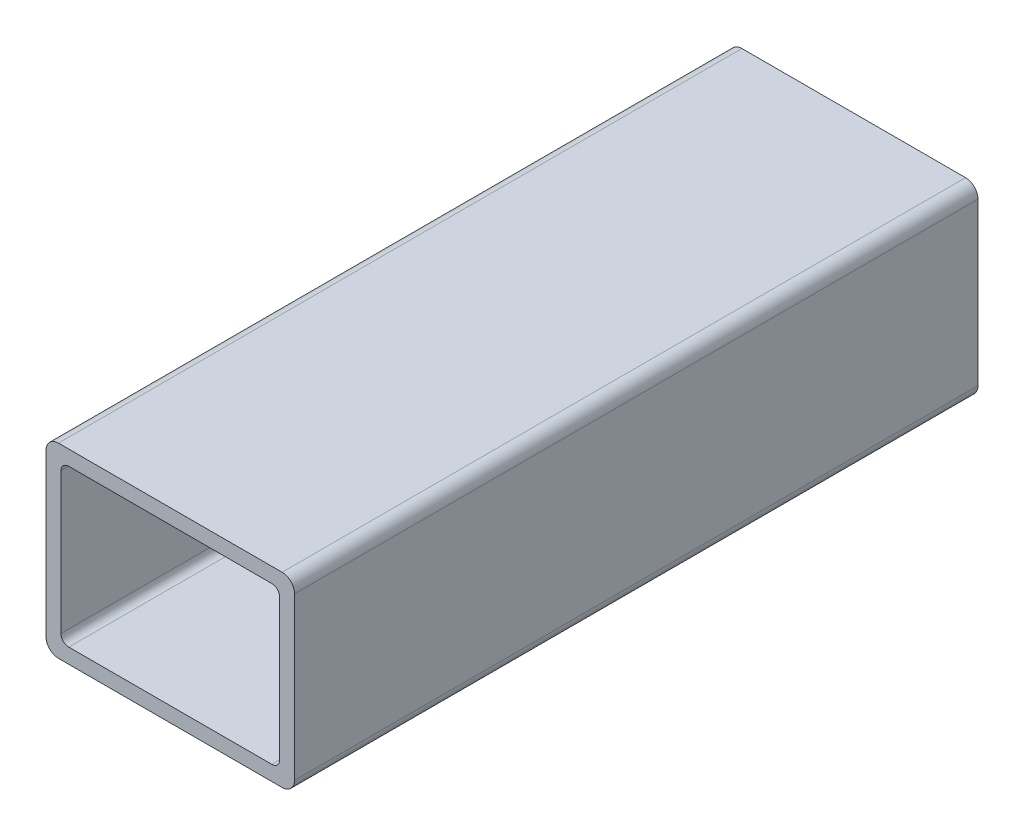
SolidWorks part; units mm, degrees
ref_plane "Front" through (0, 0, 0) normal (0, 0, 1) x (1, 0, 0)
ref_plane "Top" through (0, 0, 0) normal (0, 1, 0) x (1, 0, 0)
ref_plane "Right" through (0, 0, 0) normal (1, 0, 0) x (0, 0, -1)
sketch "Sketch1" plane through (0, 0, 0) normal (0, 0, 1) x (1, 0, 0)
  line L0 (-22.352, 0) -> (-25.4, 0) construction
  line L1 (22.86, -19.05) -> (-22.86, -19.05)
  line L2 (25.4, -16.51) -> (25.4, 16.51)
  line L3 (22.86, 19.05) -> (-22.86, 19.05)
  line L4 (-25.4, -16.51) -> (-25.4, 16.51)
  line L5 (25.4, -19.05) -> (-25.4, 19.05) construction
  line L6 (25.4, 19.05) -> (-25.4, -19.05) construction
  line L7 (20.7518, 16.002) -> (-20.7518, 16.002)
  line L8 (22.352, 14.4018) -> (22.352, -14.4018)
  line L9 (20.7518, -16.002) -> (-20.7518, -16.002)
  line L10 (-22.352, 14.4018) -> (-22.352, -14.4018)
  line L11 (22.352, 16.002) -> (-22.352, -16.002) construction
  line L12 (22.352, -16.002) -> (-22.352, 16.002) construction
  line L13 (0, -16.002) -> (0, -19.05) construction
  line L14 (22.352, -14.4018) -> (22.352, -19.05) construction
  line L16 (22.352, -19.05) -> (25.4, -19.05) construction
  arc A0 (-20.7518, -16.002) -> (-22.352, -14.4018) centre (-20.7518, -14.4018) cw
  arc A1 (22.352, -14.4018) -> (20.7518, -16.002) centre (20.7518, -14.4018) cw
  arc A2 (20.7518, 16.002) -> (22.352, 14.4018) centre (20.7518, 14.4018) cw
  arc A3 (-20.7518, 16.002) -> (-22.352, 14.4018) centre (-20.7518, 14.4018) ccw
  arc A4 (22.86, -19.05) -> (25.4, -16.51) centre (22.86, -16.51) ccw
  arc A5 (25.4, 16.51) -> (22.86, 19.05) centre (22.86, 16.51) ccw
  arc A6 (-22.86, 19.05) -> (-25.4, 16.51) centre (-22.86, 16.51) ccw
  arc A7 (-22.86, -19.05) -> (-25.4, -16.51) centre (-22.86, -16.51) cw
  point P0 (0, 0)
  point P6 (0, 0)
  dimension "D2" = 1.6002
  dimension "D3" = 2.54
sketch "Sketch2" plane through (0, 0, 0) normal (1, 0, 0) x (0, 0, -1)
  line L0 (-152.4, 0) -> (152.4, 0) construction
  dimension "Length" = 304.8
ref_plane "Plane1" through (25.4, 0, 0) normal (1, 0, 0) x (0, 0, -1)
sketch "Sketch5" plane through (25.4, 0, 0) normal (1, 0, 0) x (0, 0, -1)
  line L0 (-152.4, 19.05) -> (-152.4, -19.05) construction
  line L1 (152.4, 19.05) -> (152.4, -19.05) construction
sketch "Sketch4" plane through (0, 0, 0) normal (0, 0, 1) x (1, 0, 0)
  line L0 (25.4, -16.51) -> (25.4, 16.51) construction
  line L1 (22.86, 19.05) -> (-22.86, 19.05) construction
  line L2 (-25.4, -16.51) -> (-25.4, 16.51) construction
  line L3 (22.86, -19.05) -> (-22.86, -19.05) construction
  line L4 (22.352, 14.4018) -> (22.352, -14.4018) construction
  line L5 (20.7518, -16.002) -> (-20.7518, -16.002) construction
  line L6 (-22.352, 14.4018) -> (-22.352, -14.4018) construction
  line L7 (20.7518, 16.002) -> (-20.7518, 16.002) construction
  line L8 (25.4, -16.51) -> (25.4, 16.51)
  line L9 (22.86, 19.05) -> (-22.86, 19.05)
  line L10 (-25.4, -16.51) -> (-25.4, 16.51)
  line L11 (22.86, -19.05) -> (-22.86, -19.05)
  line L12 (22.352, 14.4018) -> (22.352, -14.4018)
  line L13 (20.7518, -16.002) -> (-20.7518, -16.002)
  line L14 (-22.352, 14.4018) -> (-22.352, -14.4018)
  line L15 (20.7518, 16.002) -> (-20.7518, 16.002)
  arc A0 (25.4, 16.51) -> (22.86, 19.05) centre (22.86, 16.51) ccw construction
  arc A1 (-22.86, 19.05) -> (-25.4, 16.51) centre (-22.86, 16.51) ccw construction
  arc A2 (-25.4, -16.51) -> (-22.86, -19.05) centre (-22.86, -16.51) ccw construction
  arc A3 (22.86, -19.05) -> (25.4, -16.51) centre (22.86, -16.51) ccw construction
  arc A4 (20.7518, -16.002) -> (22.352, -14.4018) centre (20.7518, -14.4018) ccw construction
  arc A5 (-22.352, -14.4018) -> (-20.7518, -16.002) centre (-20.7518, -14.4018) ccw construction
  arc A6 (-20.7518, 16.002) -> (-22.352, 14.4018) centre (-20.7518, 14.4018) ccw construction
  arc A7 (22.352, 14.4018) -> (20.7518, 16.002) centre (20.7518, 14.4018) ccw construction
  arc A8 (25.4, 16.51) -> (22.86, 19.05) centre (22.86, 16.51) ccw
  arc A9 (-22.86, 19.05) -> (-25.4, 16.51) centre (-22.86, 16.51) ccw
  arc A10 (-25.4, -16.51) -> (-22.86, -19.05) centre (-22.86, -16.51) ccw
  arc A11 (22.86, -19.05) -> (25.4, -16.51) centre (22.86, -16.51) ccw
  arc A12 (20.7518, -16.002) -> (22.352, -14.4018) centre (20.7518, -14.4018) ccw
  arc A13 (-22.352, -14.4018) -> (-20.7518, -16.002) centre (-20.7518, -14.4018) ccw
  arc A14 (-20.7518, 16.002) -> (-22.352, 14.4018) centre (-20.7518, 14.4018) ccw
  arc A15 (22.352, 14.4018) -> (20.7518, 16.002) centre (20.7518, 14.4018) ccw
extrude "Boss-Extrude1" add sketch "Sketch4" along normal blind 139.7
sketch "Sketch6" plane through (0, 19.05, 0) normal (0, 1, 0) x (1, 0, 0)
  line L0 (22.86, -139.7) -> (-22.86, -139.7) construction
  line L8 (0, -139.7) -> (0, 0) construction
  line L9 (22.86, 0) -> (-22.86, 0) construction
  point P0 (0, -139.7)
equation "\"D3@Sketch1\"=\"Outside Width@Sketch1\"*.05"
equation "\"D2@Sketch1\"=\"D1@Sketch1\"*.05"
